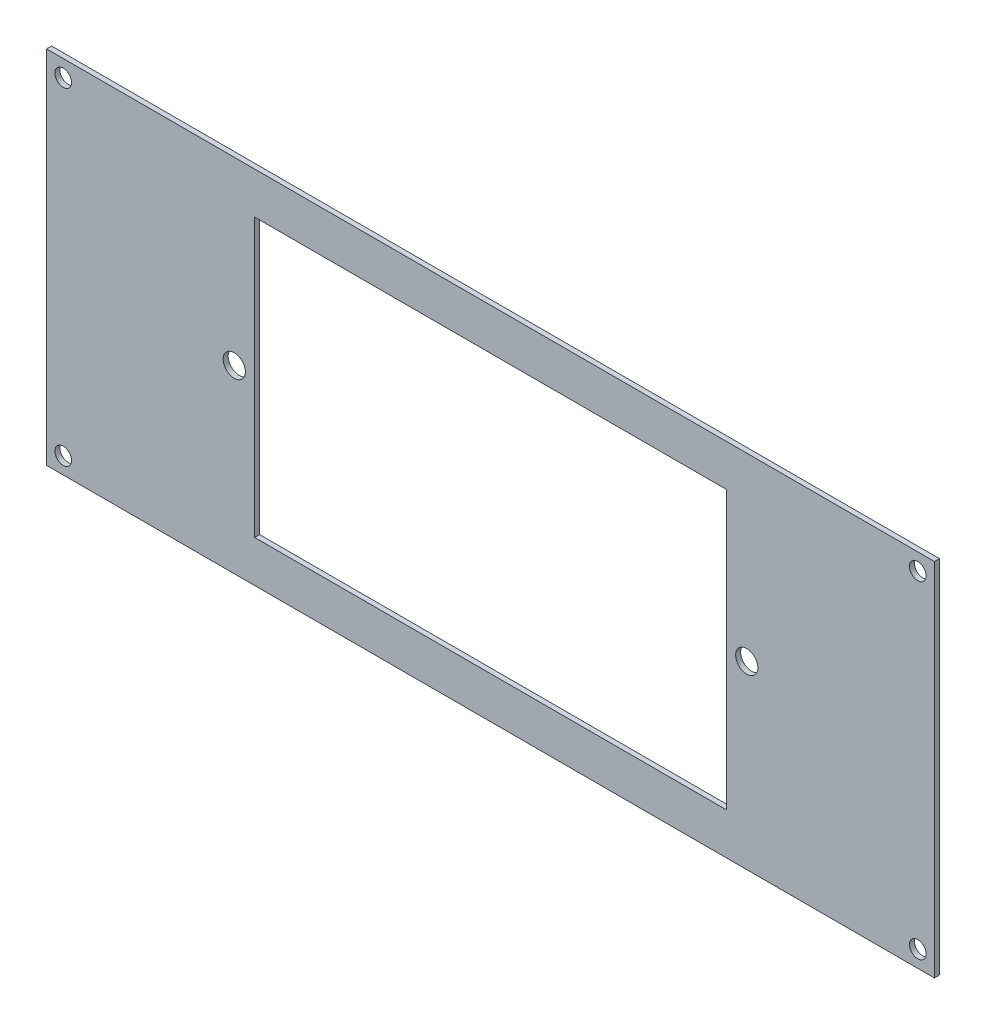
SolidWorks part; units mm, degrees
ref_plane "Plan de face" through (0, 0, 0) normal (0, 0, 1) x (1, 0, 0)
ref_plane "Plan de dessus" through (0, 0, 0) normal (0, 1, 0) x (1, 0, 0)
ref_plane "Plan de droite" through (0, 0, 0) normal (1, 0, 0) x (0, 0, -1)
sketch "Esquisse1" plane through (0, 0, 0) normal (0, 0, 1) x (1, 0, 0)
  line L1 (0, 0) -> (160, 0)
  line L2 (0, 0) -> (0, 65)
  line L3 (0, 65) -> (160, 65)
  line L4 (160, 0) -> (160, 65)
  circle A0 centre (3, 62) radius 1.5
  circle A1 centre (3, 3) radius 1.5
  circle A2 centre (157, 3) radius 1.5
  circle A3 centre (157, 62) radius 1.5
  dimension "D9" = 3
  dimension "D10" = 3
  dimension "D11" = 3
  dimension "D12" = 3
  dimension "D1" = 65
  dimension "D2" = 160
  dimension "D3" = 3
  dimension "D4" = 3
  dimension "D5" = 3
  dimension "D6" = 3
  dimension "D7" = 3
  dimension "D8" = 3
  dimension "D13" = 3
  dimension "D14" = 3
extrude "Boss.-Extru.1" add sketch "Esquisse1" along normal blind 0.9
sketch "Esquisse2" plane through (0, 0, 0.9) normal (0, 0, 1) x (1, 0, 0)
  line L1 (37.5, 57.5) -> (122.5, 57.5)
  line L2 (37.5, 57.5) -> (37.5, 7.5)
  line L3 (37.5, 7.5) -> (122.5, 7.5)
  line L4 (122.5, 57.5) -> (122.5, 7.5)
  line L5 (0, 65) -> (0, 0) construction
  line L6 (160, 65) -> (0, 65) construction
  line L7 (33.825, 32.5) -> (126.175, 32.5) construction
  circle A0 centre (33.825, 32.5) radius 2
  circle A1 centre (126.175, 32.5) radius 2
  point P6 (37.5, 32.5)
  point P7 (0, 32.5)
  point P8 (80, 57.5)
  point P11 (80, 65)
  point P16 (80, 32.5)
  point P18 (122.5, 32.5)
  dimension "D3" = 4
  dimension "D4" = 4
  dimension "D1" = 85
  dimension "D2" = 50
  dimension "D5" = 92.35
extrude "Enlèv. mat.-Extru.1" cut sketch "Esquisse2" against normal blind 0.9 contours L4 L1 L2 L3 | A0 | A1 region at (80, 32.5, 0.9)
